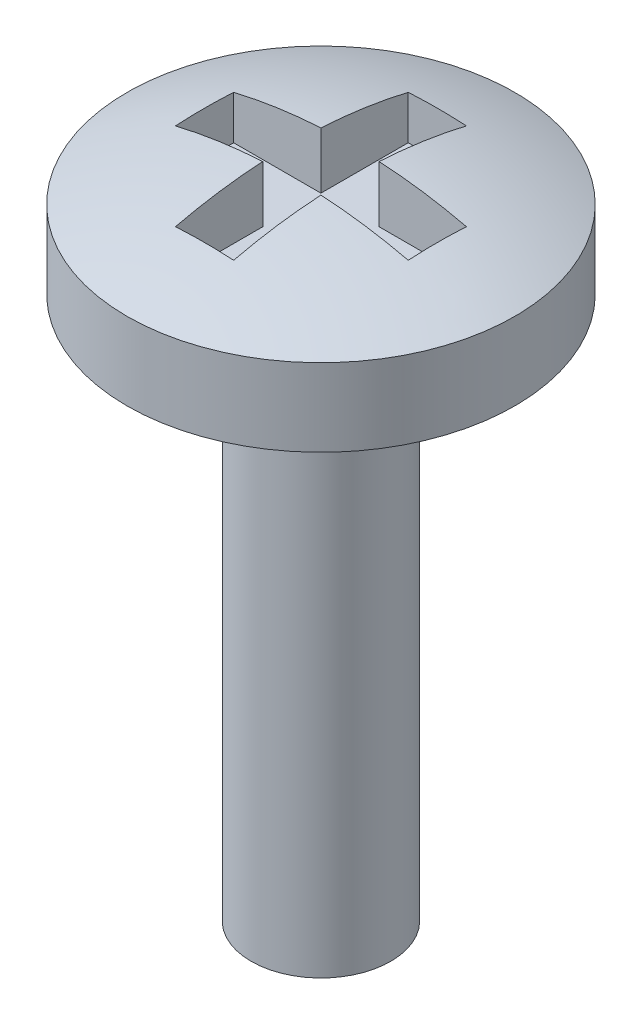
SolidWorks part; units mm, degrees
material "1023 Carbon Steel Sheet (SS)"
ref_plane "Front Plane" through (0, 0, 0) normal (0, 0, 1) x (1, 0, 0)
ref_plane "Top Plane" through (0, 0, 0) normal (0, 1, 0) x (1, 0, 0)
ref_plane "Right Plane" through (0, 0, 0) normal (1, 0, 0) x (0, 0, -1)
ref_plane "Top Plane1" through (0, 8.5, 0) normal (0, 1, 0) x (1, 0, 0)
sketch "Sketch1" plane through (0, 0, 0) normal (0, 1, 0) x (1, 0, 0)
  circle A0 centre (0, 0) radius 0.9
  dimension "D1" = 1.8
extrude "Boss-Extrude1" add sketch "Sketch1" along normal blind 7
sketch "Sketch2" plane through (0, 7, 0) normal (0, 1, 0) x (1, 0, 0)
  circle A0 centre (0, 0) radius 2.5
  dimension "D1" = 5
extrude "Boss-Extrude2" add sketch "Sketch2" along normal blind 1
dome "Dome1" faces to dome 1 distance 0.5 reverse direction no elliptical dome no face at (0, 8, 2.5) parameters "D1"=0.5
sketch "Sketch3" plane through (0, 8.5, 0) normal (0, 1, 0) x (1, 0, 0)
  line L0 (-2.5, 0) -> (2.5, 0) construction
  line L1 (0, 2.5) -> (0, -2.5) construction
  line L2 (-1.5, 0.375) -> (1.5, -0.375) construction
  line L3 (-1.5, 0.375) -> (1.5, 0.375)
  line L4 (-1.5, 0.375) -> (-1.5, -0.375)
  line L5 (-1.5, -0.375) -> (1.5, -0.375)
  line L6 (1.5, 0.375) -> (1.5, -0.375)
  line L7 (0.375, 1.5) -> (-0.375, -1.5) construction
  line L8 (-0.375, 1.5) -> (0.375, 1.5)
  line L9 (-0.375, 1.5) -> (-0.375, -1.5)
  line L10 (-0.375, -1.5) -> (0.375, -1.5)
  line L11 (0.375, 1.5) -> (0.375, -1.5)
  circle A0 centre (0, 0) radius 2.5 construction
  dimension "D1" = 1.5
  dimension "D2" = 1.5
  dimension "D3" = 0.75
  dimension "D4" = 0.75
extrude "Cut-Extrude1" cut sketch "Sketch3" against normal blind 0.75 contours L9 L3 L4 L5 | L11 L3 L9 L5 | L11 L8 L9 L3 | L3 L11 L5 L6 | L11 L5 L9 L10 region at (-0.9375, 8.5, 0) region at (0, 8.5, -0.9375) region at (0, 8.5, 0) region at (0.9375, 8.5, 0) region at (0, 8.5, 0.9375)
sketch "Sketch4" plane through (0, 0, 0) normal (0, -1, 0) x (1, 0, 0)
  point P0 (0, 0)
